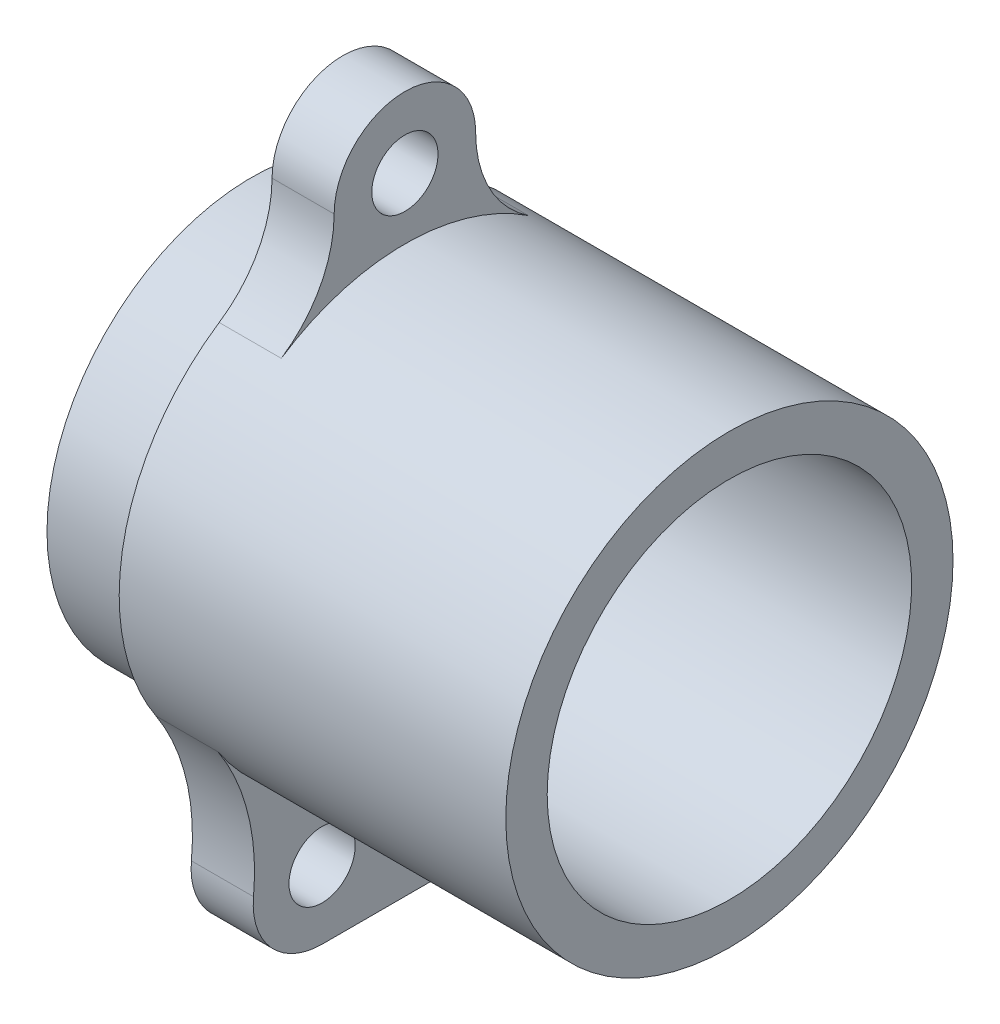
SolidWorks part; units mm, degrees
material "6061-T6 (SS)"
ref_plane "Front Plane" through (0, 0, 0) normal (0, 0, 1) x (1, 0, 0)
ref_plane "Top Plane" through (0, 0, 0) normal (0, 1, 0) x (1, 0, 0)
ref_plane "Right Plane" through (0, 0, 0) normal (1, 0, 0) x (0, 0, -1)
other "Center of Mass"
sketch "Sketch1" plane through (0, 0, 0) normal (1, 0, 0) x (0, 0, -1)
  line L0 (0, 0) -> (0, 21.8486) construction
  line L1 (2.713, 17.1496) -> (5.4259, 21.8486) construction
  line L2 (5.4259, 21.8486) -> (2.713, 26.5476) construction
  line L3 (2.713, 26.5476) -> (-2.713, 26.5476) construction
  line L4 (-2.713, 26.5476) -> (-5.4259, 21.8486) construction
  line L5 (-5.4259, 21.8486) -> (-2.713, 17.1496) construction
  line L6 (-2.713, 17.1496) -> (2.713, 17.1496) construction
  line L7 (-2.3884, -17.1978) -> (-7.5802, -15.6208) construction
  line L8 (-7.5802, -15.6208) -> (-11.5417, -19.3285) construction
  line L9 (-11.5417, -19.3285) -> (-10.3116, -24.6131) construction
  line L10 (-10.3116, -24.6131) -> (-5.1198, -26.1901) construction
  line L11 (-5.1198, -26.1901) -> (-1.1583, -22.4824) construction
  line L12 (-1.1583, -22.4824) -> (-2.3884, -17.1978) construction
  line L13 (7.5802, -15.6208) -> (2.3884, -17.1978) construction
  line L14 (2.3884, -17.1978) -> (1.1583, -22.4824) construction
  line L15 (1.1583, -22.4824) -> (5.1198, -26.1901) construction
  line L16 (5.1198, -26.1901) -> (10.3116, -24.6131) construction
  line L17 (10.3116, -24.6131) -> (11.5417, -19.3285) construction
  line L18 (11.5417, -19.3285) -> (7.5802, -15.6208) construction
  line L19 (-6.35, -20.9055) -> (6.35, -20.9055) construction
  line L20 (6.35, -26.1901) -> (-6.35, -26.1901)
  circle A0 centre (0, 0) radius 13.9746
  circle A1 centre (0, 0) radius 17.1496 construction
  circle A2 centre (0, 21.8486) radius 4.699 construction
  circle A3 centre (-6.35, -20.9055) radius 4.699 construction
  circle A4 centre (6.35, -20.9055) radius 4.699 construction
  arc A6 (5.4259, 21.8486) -> (9.4818, 14.29) centre (14.4971, 21.8486) ccw
  arc A7 (-5.4259, 21.8486) -> (-9.4818, 14.29) centre (-14.4971, 21.8486) cw
  arc A8 (-9.4818, 14.29) -> (-14.3319, -9.4184) centre (0, 0) ccw
  arc A9 (9.4818, 14.29) -> (14.3319, -9.4184) centre (0, 0) cw
  arc A10 (14.3319, -9.4184) -> (11.6105, -20.401) centre (28.5693, -18.7747) ccw
  arc A11 (11.6105, -20.401) -> (6.35, -26.1901) centre (6.35, -20.9055) cw
  arc A12 (-14.3319, -9.4184) -> (-11.6105, -20.401) centre (-28.5693, -18.7747) cw
  arc A13 (-11.6105, -20.401) -> (-6.35, -26.1901) centre (-6.35, -20.9055) ccw
  arc A15 (-5.4259, 21.8486) -> (5.4259, 21.8486) centre (0, 21.8486) cw
  circle A16 centre (0, 21.8486) radius 2.54
  circle A17 centre (-6.35, -20.9055) radius 2.54
  circle A18 centre (6.35, -20.9055) radius 2.54
  dimension "D1" = 27.9492
  dimension "D5" = 5.08
  dimension "D2" = 3.175
  dimension "D3" = 9.398
  dimension "D4" = 12.7
extrude "Boss-Extrude1" add sketch "Sketch1" along normal blind 4.7625
sketch "Sketch2" plane through (4.7625, 0, 0) normal (1, 0, 0) x (0, 0, -1)
  circle A0 centre (0, 0) radius 13.9746
  circle A1 centre (0, 0) radius 17.1496
  arc A2 (-9.4818, 14.29) -> (-14.3319, -9.4184) centre (0, 0) ccw construction
  circle A3 centre (0, 0) radius 13.9746 construction
extrude "Boss-Extrude2" add sketch "Sketch2" along normal offset from surface (24.8875 mm away) 36
sketch "Sketch3" plane through (0, 0, 0) normal (-1, 0, 0) x (0, 0, 1)
  circle A0 centre (0, 0) radius 14.1
  circle A1 centre (0, 0) radius 15.6875
  dimension "D1" = 1.5875
  dimension "D2" = 28.2
extrude "Boss-Extrude3" add sketch "Sketch3" along normal blind 7
equation "\"motor diameter\"= 28mm"
equation "\"D1@Sketch1\"=\"motor diameter\"-0.002in"
equation "\"D1@Boss-Extrude3\"=7mm"
